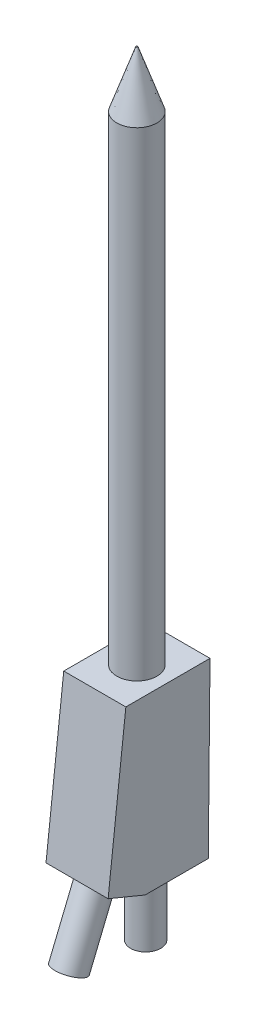
SolidWorks part; units mm, degrees
ref_plane "Ebene vorne" through (0, 0, 0) normal (0, 0, 1) x (1, 0, 0)
ref_plane "Ebene oben" through (0, 0, 0) normal (0, 1, 0) x (1, 0, 0)
ref_plane "Ebene rechts" through (0, 0, 0) normal (1, 0, 0) x (0, 0, -1)
sketch "Sketch1" plane through (0, 0, 0) normal (0, 1, 0) x (1, 0, 0)
  circle A0 centre (0, 0) radius 2
  dimension "D1" = 4
extrude "Boss-Extrude1" add sketch "Sketch1" along normal blind 50
sketch "Sketch2" plane through (0, 0, 0) normal (0, 0, 1) x (1, 0, 0)
  line L0 (0, 55.6) -> (0, 50)
  line L1 (0, 50) -> (2, 50)
  line L2 (0, 55.6) -> (0.0785, 55.6)
  line L3 (0.0785, 55.6) -> (2, 50)
  line L4 (2, 50) -> (-2, 50) construction
  line L5 (-2, 50) -> (2, 50) construction
  point P8 (0, 50)
  dimension "D1" = 5.6
revolve "Revolve1" add sketch "Sketch2" angle 360 about L0
sketch "Sketch3" plane through (0, 0, 0) normal (1, 0, 0) x (0, 0, -1)
  line L0 (-4.2, 2.1715) -> (4.2, 2.1715)
  line L1 (4.2, 2.1715) -> (4.0299, -15.0483)
  line L2 (4.0299, -15.0483) -> (-2.2701, -15.0483)
  line L3 (-2.2701, -15.0483) -> (-5.9701, -13.5285)
  line L4 (-5.9701, -13.5285) -> (-4.2, 2.1715)
  line L5 (0, 2.1715) -> (0, -22.4515) construction
  dimension "D1" = 15.7
  dimension "D2" = 8.4
  dimension "D3" = 10
  dimension "D4" = 4
  dimension "D5" = 6.3
extrude "Boss-Extrude2" add sketch "Sketch3" along normal mid plane 6.2
sketch "Sketch4" plane through (0, -13.6736, 5.6168) normal (0, -0.925, 0.38) x (-1, 0, 0)
  line L0 (3.1, 1.618) -> (-3.1, 1.618) construction
  line L1 (3.1, -0.382) -> (3.1, 3.618) construction
  line L2 (-3.1, -0.382) -> (-3.1, 3.618) construction
  line L3 (0, -0.382) -> (0, 3.618) construction
  line L4 (-3.1, -0.382) -> (3.1, -0.382) construction
  line L5 (-3.1, 3.618) -> (3.1, 3.618) construction
  circle A0 centre (0, 1.618) radius 1.5
  dimension "D1" = 3
extrude "Boss-Extrude3" add sketch "Sketch4" along normal blind 7 contours A0
sketch "Sketch5" plane through (0, -15.0483, 0) normal (0, -1, 0) x (-1, 0, 0)
  line L0 (0, 4.0299) -> (0, -2.2701) construction
  line L1 (-3.1, 4.0299) -> (3.1, 4.0299) construction
  line L2 (-3.1, -2.2701) -> (3.1, -2.2701) construction
  line L3 (3.1, 0.8799) -> (-3.1, 0.8799) construction
  line L4 (3.1, -2.2701) -> (3.1, 4.0299) construction
  line L5 (-3.1, -2.2701) -> (-3.1, 4.0299) construction
  circle A0 centre (0, 0.8799) radius 1.5
  point P15 (0, 0.8799)
  dimension "D1" = 3
extrude "Boss-Extrude4" add sketch "Sketch5" along normal blind 7
